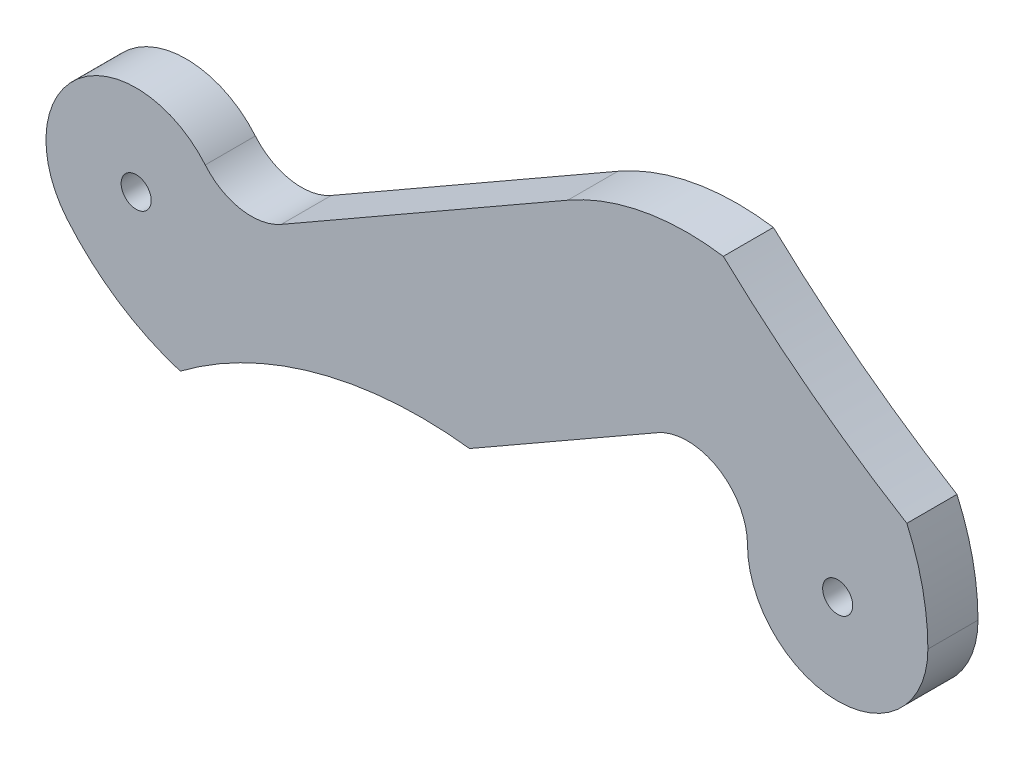
SolidWorks part; units mm, degrees
ref_plane "Plan de face" through (0, 0, 0) normal (0, 0, 1) x (1, 0, 0)
ref_plane "Plan de dessus" through (0, 0, 0) normal (0, 1, 0) x (1, 0, 0)
ref_plane "Plan de droite" through (0, 0, 0) normal (1, 0, 0) x (0, 0, -1)
sketch "Esquisse1" plane through (0, 0, 0) normal (0, 0, 1) x (1, 0, 0)
  line L0 (0, 0) -> (70, 0) construction
  line L1 (0, 0) -> (0, 15) construction
  line L2 (0, 0) -> (11.4907, 9.6418) construction
  line L3 (70, -15) -> (70, 0) construction
  line L4 (70, 0) -> (55, 0) construction
  line L5 (14.4741, 4.4361) -> (43.0662, 20.8227)
  line L6 (23.4245, -11.1809) -> (52.0166, 5.2057)
  arc A0 (11.4907, 9.6418) -> (0, 15) centre (0, 0) ccw construction
  arc A1 (16.0869, 13.4985) -> (0, 21) centre (0, 0) ccw construction
  circle A2 centre (70, 0) radius 1.5
  circle A3 centre (0, 0) radius 1.5
  arc A4 (6.8944, 5.7851) -> (0, 9) centre (0, 0) ccw construction
  arc A5 (6.8944, 5.7851) -> (16.0869, 13.4985) centre (11.4907, 9.6418) ccw construction
  arc A6 (0, 21) -> (0, 9) centre (0, 15) ccw construction
  arc A7 (55, 0) -> (70, -15) centre (70, 0) ccw construction
  arc A8 (49, 0) -> (70, -21) centre (70, 0) ccw construction
  arc A9 (61, 0) -> (70, -9) centre (70, 0) ccw construction
  arc A10 (61, 0) -> (49, 0) centre (55, 0) ccw construction
  arc A11 (70, -21) -> (70, -9) centre (70, -15) ccw construction
  arc A12 (6.8944, 5.7851) -> (-6.8944, -5.7851) centre (0, 0) ccw
  arc A13 (61, 0) -> (79, 0) centre (70, 0) ccw
  arc A14 (6.8944, 5.7851) -> (14.4741, 4.4361) centre (11.4907, 9.6418) ccw
  arc A15 (61, 0) -> (52.0166, 5.2057) centre (55, 0) ccw
  arc A16 (-6.8944, -5.7851) -> (23.4245, -11.1809) centre (11.4907, 9.6418) ccw
  arc A17 (79, 0) -> (43.0662, 20.8227) centre (55, 0) ccw
  point P6 (6.3393, 13.5946)
  point P15 (59.3934, -10.6066)
  dimension "D1" = 3
  dimension "D2" = 70
  dimension "D3" = 15
  dimension "D6" = 50
  dimension "D7" = 90
  dimension "D8" = 6
  dimension "D4" = 90
extrude "Boss.-Extru.1" add sketch "Esquisse1" along normal blind 5
sketch "Esquisse2" plane through (0, 0, 5) normal (0, 0, 1) x (1, 0, 0)
  line L1 (23.4245, -11.1809) -> (52.0166, 5.2057) construction
  arc A0 (4.4015, -13.2873) -> (33.2657, -5.5407) centre (28.4513, -45.2499) cw
  arc A1 (-6.8944, -5.7851) -> (23.4245, -11.1809) centre (11.4907, 9.6418) ccw construction
  arc A2 (4.4015, -13.2873) -> (33.2657, -5.5407) centre (13.6384, 9.9437) ccw
  arc A3 (58.5852, 23.7307) -> (76.9, 9.8178) centre (134.56, 104.7323) ccw
  arc A4 (79, 0) -> (43.0662, 20.8227) centre (55, 0) ccw construction
  arc A5 (58.5852, 23.7307) -> (76.9, 9.8178) centre (55, 0) cw
  circle A6 centre (70, 0) radius 1.5 construction
  dimension "D1" = 40
  dimension "D2" = 12
  dimension "D3" = 23
extrude "Enlèv. mat.-Extru.1" cut sketch "Esquisse2" against normal blind 10
